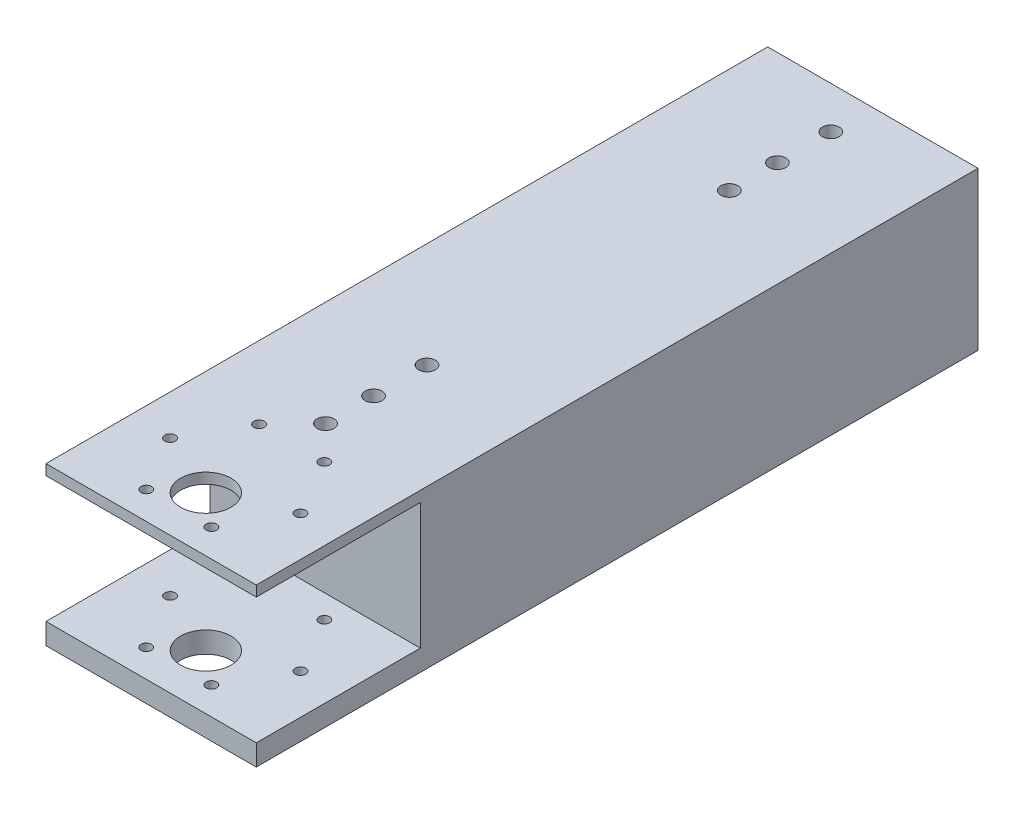
SolidWorks part; units mm, degrees
material "Nylon 101"
ref_plane "Front" through (0, 0, 0) normal (0, 0, 1) x (1, 0, 0)
ref_plane "Top" through (0, 0, 0) normal (0, 1, 0) x (1, 0, 0)
ref_plane "Right" through (0, 0, 0) normal (1, 0, 0) x (0, 0, -1)
sketch "Sketch1" plane through (0, 0, 0) normal (0, 1, 0) x (1, 0, 0)
  line L1 (-25, 0) -> (25, 0)
  line L2 (-25, 0) -> (-25, 171.6)
  line L3 (-25, 171.6) -> (25, 171.6)
  line L4 (25, 0) -> (25, 171.6)
  circle A15 centre (0, 148.9) radius 2
  circle A16 centre (0, 161.6) radius 2
  circle A17 centre (0, 137.47) radius 2
  circle A18 centre (0, 52.888) radius 2
  circle A19 centre (0, 65.588) radius 2
  circle A20 centre (0, 41.458) radius 2
  dimension "D10" = 4
  dimension "D16" = 10
  dimension "D1" = 50
  dimension "D9" = 148.9
  dimension "D11" = 11.43
  dimension "D12" = 12.7
  dimension "D13" = 12.7
  dimension "D14" = 11.43
  dimension "D15" = 96.012
extrude "Boss-Extrude1" add sketch "Sketch1" along normal blind 37.5
sketch "Sketch2" plane through (0, 0, 0) normal (0, -1, 0) x (1, 0, 0)
  line L0 (25, 0) -> (25, -171.6) construction
  line L1 (-25, 0) -> (25, 0)
  line L2 (-25, 0) -> (-25, -39)
  line L3 (-25, -39) -> (25, -39)
  line L4 (25, 0) -> (25, -39)
  circle A0 centre (0, -20) radius 15.5 construction
  circle A1 centre (0, -20) radius 18.4 construction
  circle A2 centre (0, -13) radius 3 construction
  circle A3 centre (0, -13) radius 6
  circle A4 centre (-15.5, -20) radius 1.25
  circle A10 centre (-7.75, -6.5766) radius 1.25
  circle A11 centre (7.75, -6.5766) radius 1.25
  circle A12 centre (15.5, -20) radius 1.25
  circle A13 centre (7.75, -33.4234) radius 1.25
  circle A14 centre (-7.75, -33.4234) radius 1.25
  dimension "D1" = 31
  dimension "D2" = 36.8
  dimension "D3" = 12
  dimension "D5" = 6
  dimension "D6" = 2.5
  dimension "D7" = 20
  dimension "D8" = 39
  dimension "D4" = 7
sketch "Sketch3" plane through (0, 37.5, 0) normal (0, 1, 0) x (1, 0, 0)
  line L0 (0, 171.6) -> (0, 166.252) construction
  line L1 (-35, 171.6) -> (35, 171.6)
  line L2 (-35, 171.6) -> (-35, 141.6)
  line L3 (-35, 141.6) -> (35, 141.6)
  line L4 (35, 171.6) -> (35, 141.6)
  line L5 (25, 171.6) -> (-25, 171.6) construction
  line L6 (-25, 171.6) -> (-25, 0) construction
  line L7 (25, 0) -> (25, 171.6) construction
  line L8 (-25, 171.6) -> (-25, 141.6)
  line L9 (25, 141.6) -> (25, 171.6)
  line M5 (-25, 171.6) -> (-25, 0)
  line M7 (25, 0) -> (25, 171.6)
  dimension "D1" = 70
  dimension "D2" = 30
extrude "Boss-Extrude2" [suppressed] add sketch "Sketch3" against normal blind 25 contours L2 L3 L1 M5 | L4 L1 L3 M7
extrude "Cut-Extrude4" cut sketch "Sketch2" against normal blind 30 from offset 5 offset against normal yes
extrude "Cut-Extrude5" cut sketch "Sketch2<3>" against normal through all contours A14 | A13 | A3 | A10 | A11 | A4 | A12 region at (0, 0, -13) region at (-15.5, 0, -20) region at (-7.75, 0, -6.5766) region at (7.75, 0, -6.5766) region at (15.5, 0, -20) region at (7.75, 0, -33.4234) region at (-7.75, 0, -33.4234)
sketch "Sketch2<3>" plane through (0, 0, 0) normal (0, -1, 0) x (1, 0, 0) same geometry as "Sketch2"
sketch "Sketch4" [suppressed] plane through (0, 0, 0) normal (0, -1, 0) x (1, 0, 0)
  line L0 (11.115, -141.6) -> (35, -141.6) construction
  line L1 (35, -171.6) -> (35, -141.6) construction
  line L2 (7.8056, -11.2472) -> (37.8056, -144.8472) construction
  line L3 (0, -171.6) -> (0, -167.9906) construction
  line L4 (35, -171.6) -> (-35, -171.6) construction
  circle A0 centre (-30, -146.6) radius 8
  circle A1 centre (30, -146.6) radius 8
  circle A2 centre (0, -13) radius 8
  circle A3 centre (30, -146.6) radius 1.25
  circle A4 centre (-30, -146.6) radius 1.25
  dimension "D1" = 16
  dimension "D4" = 2.5
  dimension "D2" = 5
  dimension "D3" = 5
extrude "Cut-Extrude6" [suppressed] cut sketch "Sketch4" against normal through all contours A3 | A4
sketch "Sketch5" [suppressed] plane through (-35, 0, 0) normal (-1, 0, 0) x (0, 0, 1)
  circle A0 centre (-148.6114, 14.427) radius 7.7115
